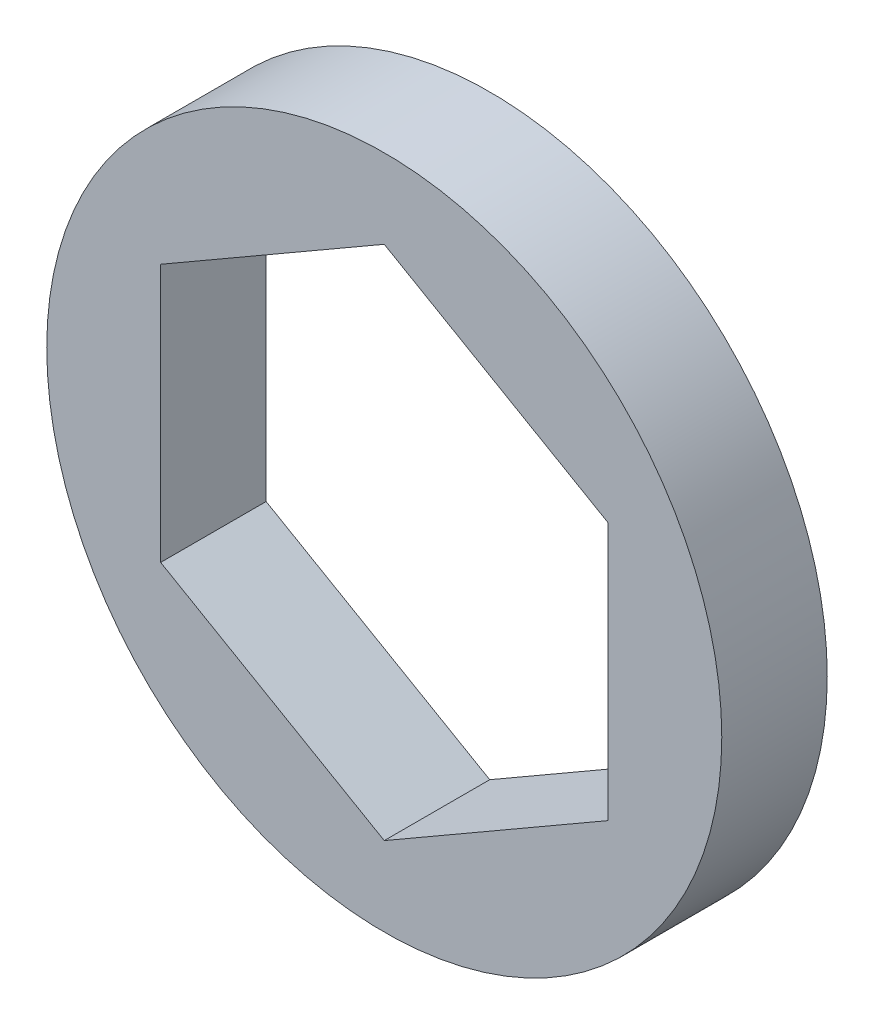
SolidWorks part; units mm, degrees
material "Nylon 101"
ref_plane "Front Plane" through (0, 0, 0) normal (0, 0, 1) x (1, 0, 0)
ref_plane "Top Plane" through (0, 0, 0) normal (0, 1, 0) x (1, 0, 0)
ref_plane "Right Plane" through (0, 0, 0) normal (1, 0, 0) x (0, 0, -1)
sketch "Sketch1" plane through (0, 0, 0) normal (0, 0, 1) x (1, 0, 0)
  line L1 (0, 7.7723) -> (-6.731, 3.8861)
  line L2 (-6.731, 3.8861) -> (-6.731, -3.8861)
  line L3 (-6.731, -3.8861) -> (0, -7.7723)
  line L4 (0, -7.7723) -> (6.731, -3.8861)
  line L5 (6.731, -3.8861) -> (6.731, 3.8861)
  line L6 (6.731, 3.8861) -> (0, 7.7723)
  circle A0 centre (0, 0) radius 10.16
  circle A1 centre (0, 0) radius 6.731 construction
  point P3 (0, 0)
  point P11 (0, 0)
  point P12 (0, 0)
  dimension "D1" = 20.32
  dimension "D2" = 13.462
extrude "Boss-Extrude1" add sketch "Sketch1" along normal mid plane 3.175
